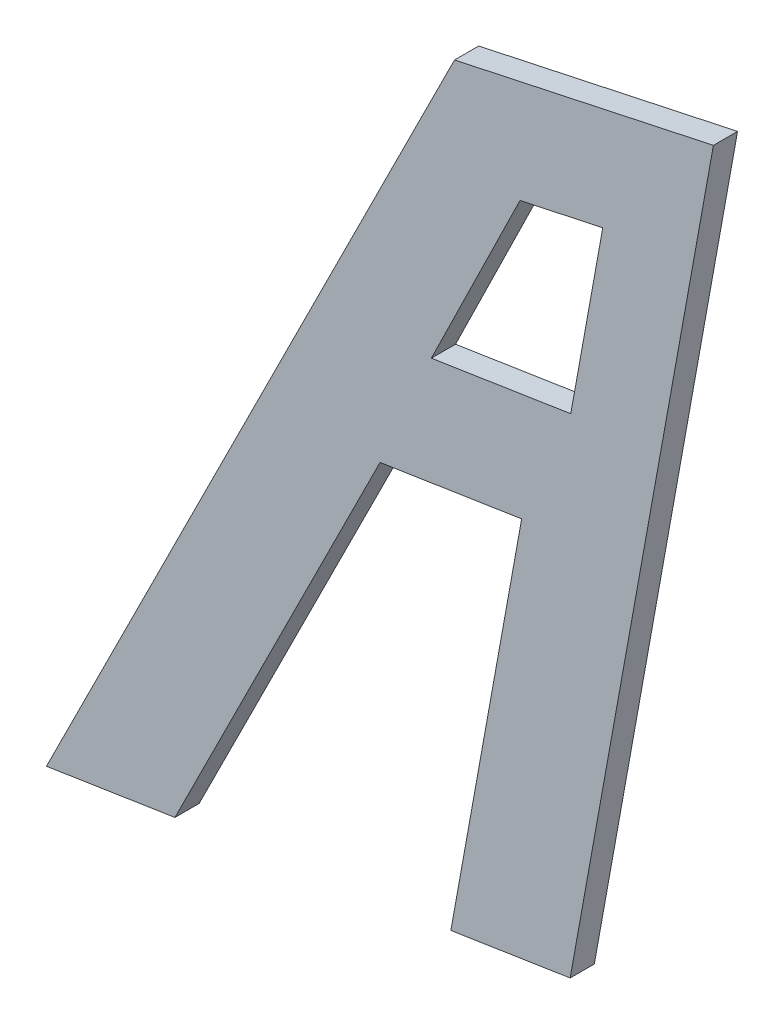
SolidWorks part; units mm, degrees
ref_plane "Front Plane" through (0, 0, 0) normal (0, 0, 1) x (1, 0, 0)
ref_plane "Top Plane" through (0, 0, 0) normal (0, 1, 0) x (1, 0, 0)
ref_plane "Right Plane" through (0, 0, 0) normal (1, 0, 0) x (0, 0, -1)
sketch "Sketch10" plane through (0, 0, 0) normal (0, 0, 1) x (1, 0, 0)
  line L0 (-181.4782, 18.7888) -> (-224.3667, -66.9392)
  line L1 (-224.3667, -66.9392) -> (-210.8609, -64.8454)
  line L2 (-210.8609, -64.8454) -> (-189.3053, -21.7589)
  line L3 (-189.3053, -21.7589) -> (-174.4233, -19.4518)
  line L4 (-174.4233, -19.4518) -> (-181.8643, -60.6338)
  line L5 (-181.8643, -60.6338) -> (-169.3252, -58.6899)
  line L6 (-169.3252, -58.6899) -> (-154.2723, 24.6199)
  line L7 (-154.2723, 24.6199) -> (-181.4782, 18.7888)
  line L8 (-174.5962, 9.4402) -> (-165.8997, 11.3041)
  line L9 (-165.8997, 11.3041) -> (-169.2614, -7.3008)
  line L10 (-169.2614, -7.3008) -> (-183.9126, -9.5721)
  line L11 (-183.9126, -9.5721) -> (-174.5962, 9.4402)
  line L12 (-183.9126, -9.5721) -> (-181.8643, -9.2546)
extrude "Boss-Extrude2" add sketch "Sketch10" along normal blind 2.54 contours L11 L10 L9 L8 | L0 L1 L2 L3 L4 L5 L6 L7 region at (-173.6618, 0.1435, 0)
